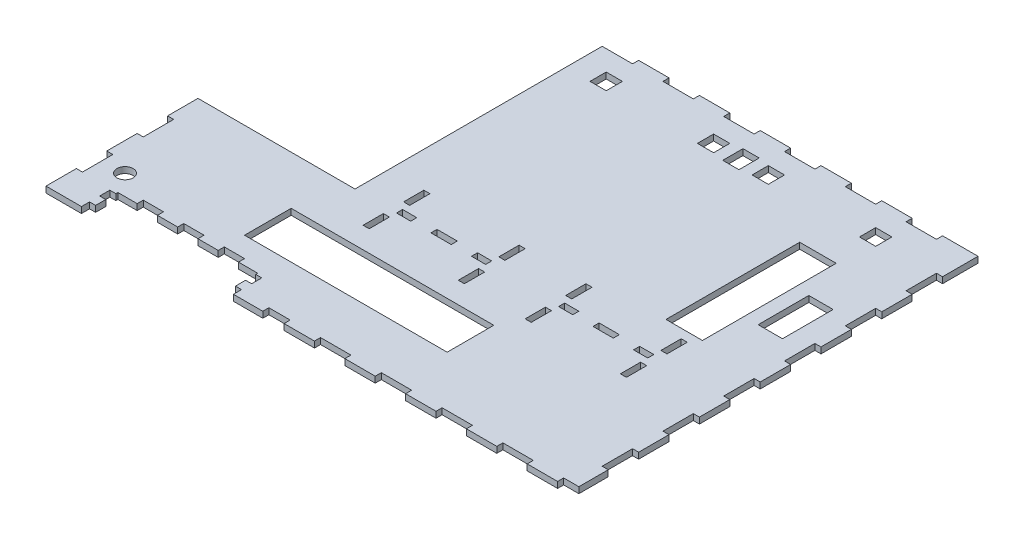
SolidWorks part; units mm, degrees
ref_plane "Alzado" through (0, 0, 0) normal (0, 0, 1) x (1, 0, 0)
ref_plane "Planta" through (0, 0, 0) normal (0, 1, 0) x (1, 0, 0)
ref_plane "Vista lateral" through (0, 0, 0) normal (1, 0, 0) x (0, 0, -1)
sketch "Croquis1" plane through (0, 0, 0) normal (0, 1, 0) x (1, 0, 0)
  line L0 (17.5, 79) -> (20.5, 79)
  line L1 (60, 83) -> (50, 83)
  line L2 (0, 265) -> (17.5, 265) construction
  line L3 (260, 265) -> (260, 247.5)
  line L4 (252.5, 65) -> (237.5, 65)
  line L5 (50, 83) -> (50, 80)
  line L6 (50, 80) -> (40, 80)
  line L7 (40, 80) -> (40, 83)
  line L8 (84.3736, 80) -> (89.5, 80)
  line L9 (40, 83) -> (30, 83)
  line L10 (17.5, 69) -> (20.5, 69)
  line L11 (0, 65) -> (17.5, 65)
  line L12 (92.5, 69) -> (92.5, 65)
  line L13 (20.5, 74) -> (17.5, 74)
  line L14 (92.5, 69) -> (89.5, 69)
  line L15 (30, 83) -> (30, 80)
  line L16 (89.5, 69) -> (89.5, 74)
  line L17 (92.5, 74) -> (92.5, 79)
  line L18 (115, 143) -> (125, 143)
  line L19 (80, 80) -> (84.3736, 80)
  line L20 (89.5, 80) -> (89.5, 79)
  line L21 (30, 80) -> (25.6264, 80)
  line L22 (115, 140) -> (125, 140)
  line L23 (17.5, 69) -> (17.5, 65)
  line L24 (80, 83) -> (80, 80)
  line L25 (89.5, 74) -> (92.5, 74)
  line L26 (70, 83) -> (80, 83)
  line L27 (120, 93) -> (70, 93)
  line L28 (177.5, 65) -> (177.5, 68)
  line L29 (177.5, 68) -> (162.5, 68)
  line L30 (162.5, 68) -> (162.5, 65)
  line L31 (162.5, 65) -> (147.5, 65)
  line L32 (147.5, 65) -> (147.5, 68)
  line L33 (147.5, 68) -> (132.5, 68)
  line L34 (132.5, 68) -> (132.5, 65)
  line L35 (132.5, 65) -> (117.5, 65)
  line L36 (117.5, 65) -> (117.5, 68)
  line L37 (117.5, 68) -> (107, 68)
  line L38 (107, 68) -> (107, 65)
  line L39 (70, 80) -> (70, 83)
  line L40 (92.5, 65) -> (107, 65)
  line L41 (260, 157.5) -> (257, 157.5)
  line L42 (252.5, 68) -> (260, 68)
  line L43 (252.5, 65) -> (252.5, 68)
  line L44 (237.5, 68) -> (237.5, 65)
  line L45 (222.5, 68) -> (237.5, 68)
  line L46 (222.5, 65) -> (222.5, 68)
  line L47 (207.5, 68) -> (207.5, 65)
  line L48 (192.5, 68) -> (207.5, 68)
  line L49 (192.5, 65) -> (192.5, 68)
  line L50 (257, 157.5) -> (257, 142.5)
  line L51 (257, 142.5) -> (260, 142.5)
  line L52 (260, 142.5) -> (260, 127.5)
  line L53 (260, 127.5) -> (257, 127.5)
  line L54 (257, 127.5) -> (257, 112.5)
  line L55 (257, 112.5) -> (260, 112.5)
  line L56 (260, 112.5) -> (260, 97.5)
  line L57 (260, 97.5) -> (257, 97.5)
  line L58 (257, 97.5) -> (257, 82.5)
  line L59 (257, 82.5) -> (260, 82.5)
  line L60 (89.5, 79) -> (92.5, 79)
  line L61 (257, 247.5) -> (260, 247.5)
  line L62 (257, 232.5) -> (257, 247.5)
  line L63 (260, 232.5) -> (257, 232.5)
  line L64 (257, 217.5) -> (260, 217.5)
  line L65 (257, 202.5) -> (257, 217.5)
  line L66 (260, 202.5) -> (257, 202.5)
  line L67 (257, 187.5) -> (260, 187.5)
  line L68 (257, 172.5) -> (257, 187.5)
  line L69 (260, 172.5) -> (257, 172.5)
  line L70 (137.5, 265) -> (137.5, 262)
  line L71 (137.5, 262) -> (152.5, 262)
  line L72 (152.5, 262) -> (152.5, 265)
  line L73 (152.5, 265) -> (167.5, 265)
  line L74 (167.5, 265) -> (167.5, 262)
  line L75 (167.5, 262) -> (182.5, 262)
  line L76 (182.5, 262) -> (182.5, 265)
  line L77 (182.5, 265) -> (197.5, 265)
  line L78 (197.5, 265) -> (197.5, 262)
  line L79 (197.5, 262) -> (212.5, 262)
  line L80 (212.5, 262) -> (212.5, 265)
  line L81 (212.5, 265) -> (227.5, 265)
  line L82 (227.5, 265) -> (227.5, 262)
  line L83 (227.5, 262) -> (242.5, 262)
  line L84 (242.5, 262) -> (242.5, 265)
  line L85 (17.5, 74) -> (17.5, 79)
  line L86 (17.5, 262) -> (17.5, 265) construction
  line L87 (32.5, 262) -> (17.5, 262) construction
  line L88 (32.5, 265) -> (32.5, 262) construction
  line L89 (47.5, 262) -> (47.5, 265) construction
  line L90 (62.5, 262) -> (47.5, 262) construction
  line L91 (62.5, 265) -> (62.5, 262) construction
  line L92 (77.5, 262) -> (77.5, 265) construction
  line L93 (92.5, 262) -> (77.5, 262)
  line L94 (92.5, 265) -> (92.5, 262)
  line L95 (107.5, 262) -> (107.5, 265)
  line L96 (122.5, 262) -> (107.5, 262)
  line L97 (122.5, 265) -> (122.5, 262)
  line L98 (0, 140) -> (3, 140)
  line L99 (3, 140) -> (3, 155) construction
  line L100 (3, 155) -> (0, 155) construction
  line L101 (0, 155) -> (0, 162.5) construction
  line L102 (0, 170) -> (3, 170) construction
  line L103 (3, 170) -> (3, 185) construction
  line L104 (3, 185) -> (0, 185) construction
  line L105 (0, 185) -> (0, 200) construction
  line L106 (0, 200) -> (3, 200) construction
  line L107 (3, 200) -> (3, 215) construction
  line L108 (3, 215) -> (0, 215) construction
  line L109 (0, 215) -> (0, 230) construction
  line L110 (0, 230) -> (3, 230) construction
  line L111 (3, 230) -> (3, 245) construction
  line L112 (3, 245) -> (0, 245) construction
  line L113 (20.5, 69) -> (20.5, 74)
  line L114 (60, 80) -> (70, 80)
  line L115 (60, 83) -> (60, 80)
  line L116 (20.5, 79) -> (20.5, 80)
  line L117 (20.5, 80) -> (25.6264, 80)
  line L118 (70, 93) -> (70, 116)
  line L119 (32.5, 265) -> (47.5, 265) construction
  line L120 (3, 80) -> (0, 80)
  line L121 (3, 95) -> (3, 80)
  line L122 (0, 95) -> (3, 95)
  line L123 (3, 110) -> (0, 110)
  line L124 (3, 125) -> (3, 110)
  line L125 (0, 125) -> (3, 125)
  line L126 (70, 116) -> (170, 116)
  line L127 (170, 116) -> (170, 93)
  line L128 (62.5, 265) -> (77.5, 265) construction
  line L129 (92.5, 265) -> (107.5, 265)
  line L130 (122.5, 265) -> (137.5, 265)
  line L131 (170, 93) -> (120, 93)
  line L132 (195, 143) -> (205, 143)
  line L133 (98, 156.5) -> (98, 146.5)
  line L134 (242.5, 265) -> (260, 265)
  line L135 (0, 245) -> (0, 265) construction
  line L136 (98, 136.5) -> (95, 136.5)
  line L137 (95, 136.5) -> (95, 126.5)
  line L138 (95, 126.5) -> (98, 126.5)
  line L139 (0, 125) -> (0, 140)
  line L140 (0, 95) -> (0, 110)
  line L141 (0, 65) -> (0, 80)
  line L142 (3, 140) -> (77.5, 140)
  line L143 (105, 140) -> (98, 140)
  line L144 (98, 140) -> (98, 143)
  line L145 (98, 143) -> (105, 143)
  line L146 (105, 143) -> (105, 140)
  line L147 (95, 156.5) -> (98, 156.5)
  line L148 (95, 146.5) -> (95, 156.5)
  line L149 (98, 146.5) -> (95, 146.5)
  line L150 (192.5, 65) -> (177.5, 65)
  line L151 (222.5, 65) -> (207.5, 65)
  line L152 (260, 82.5) -> (260, 68)
  line L153 (142, 146.5) -> (145, 146.5)
  line L154 (145, 146.5) -> (145, 156.5)
  line L155 (260, 172.5) -> (260, 157.5)
  line L156 (260, 202.5) -> (260, 187.5)
  line L157 (260, 232.5) -> (260, 217.5)
  line L158 (145, 156.5) -> (142, 156.5)
  line L159 (98, 126.5) -> (98, 136.5)
  line L160 (77.5, 140) -> (77.5, 155)
  line L161 (142, 156.5) -> (142, 146.5)
  line L162 (142, 126.5) -> (142, 136.5)
  line L163 (145, 126.5) -> (142, 126.5)
  line L164 (145, 136.5) -> (145, 126.5)
  line L165 (142, 136.5) -> (145, 136.5)
  line L166 (178, 156.5) -> (178, 146.5)
  line L167 (175, 156.5) -> (178, 156.5)
  line L168 (135, 143) -> (135, 140)
  line L169 (142, 143) -> (135, 143)
  line L170 (142, 140) -> (142, 143)
  line L171 (135, 140) -> (142, 140)
  line L172 (125, 143) -> (125, 140)
  line L173 (115, 140) -> (115, 143)
  line L174 (185, 140) -> (178, 140)
  line L175 (175, 146.5) -> (175, 156.5)
  line L176 (178, 140) -> (178, 143)
  line L177 (178, 146.5) -> (175, 146.5)
  line L178 (222, 146.5) -> (225, 146.5)
  line L179 (225, 146.5) -> (225, 156.5)
  line L180 (222, 140) -> (222, 143)
  line L181 (225, 156.5) -> (222, 156.5)
  line L182 (222, 156.5) -> (222, 146.5)
  line L183 (178, 136.5) -> (175, 136.5)
  line L184 (175, 136.5) -> (175, 126.5)
  line L185 (178, 143) -> (185, 143)
  line L186 (175, 126.5) -> (178, 126.5)
  line L187 (205, 140) -> (205, 143)
  line L188 (185, 143) -> (185, 140)
  line L189 (178, 126.5) -> (178, 136.5)
  line L190 (222, 126.5) -> (222, 136.5)
  line L191 (225, 126.5) -> (222, 126.5)
  line L192 (225, 136.5) -> (225, 126.5)
  line L193 (222, 136.5) -> (225, 136.5)
  line L194 (0, 170) -> (0, 162.5) construction
  line L195 (215, 143) -> (215, 140)
  line L196 (77.5, 155) -> (77.5, 262)
  line L197 (93.5, 248) -> (93.5, 244) construction
  line L198 (89.5, 252) -> (97.5, 252)
  line L199 (215, 140) -> (222, 140)
  line L200 (195, 140) -> (205, 140)
  line L201 (89.5, 252) -> (89.5, 244)
  line L202 (89.5, 244) -> (97.5, 244)
  line L203 (97.5, 252) -> (97.5, 244)
  line L204 (222, 143) -> (215, 143)
  line L205 (195, 140) -> (195, 143)
  line L206 (89.5, 252) -> (97.5, 244) construction
  line L207 (89.5, 244) -> (97.5, 252) construction
  line L208 (146.5, 248) -> (146.5, 244) construction
  line L209 (142.5, 252) -> (150.5, 252)
  line L210 (142.5, 252) -> (142.5, 244)
  line L211 (142.5, 244) -> (150.5, 244)
  line L212 (150.5, 252) -> (150.5, 244)
  line L213 (142.5, 252) -> (150.5, 244) construction
  line L214 (142.5, 244) -> (150.5, 252) construction
  line L215 (173.5, 248) -> (173.5, 244) construction
  line L216 (169.5, 252) -> (177.5, 252)
  line L217 (169.5, 252) -> (169.5, 244)
  line L218 (169.5, 244) -> (177.5, 244)
  line L219 (177.5, 252) -> (177.5, 244)
  line L220 (169.5, 252) -> (177.5, 244) construction
  line L221 (169.5, 244) -> (177.5, 252) construction
  line L222 (226.5, 248) -> (226.5, 244) construction
  line L223 (222.5, 252) -> (230.5, 252)
  line L224 (222.5, 252) -> (222.5, 244)
  line L225 (222.5, 244) -> (230.5, 244)
  line L226 (230.5, 252) -> (230.5, 244)
  line L227 (222.5, 252) -> (230.5, 244) construction
  line L228 (222.5, 244) -> (230.5, 252) construction
  dimension "D6" = 10
  dimension "D14" = 8
  dimension "D16" = 3
  dimension "D70" = 8
  dimension "D7" = 50
  dimension "D8" = 10
  dimension "D9" = 10
  dimension "D10" = 23
  dimension "D11" = 100
  dimension "D12" = 16
  dimension "D13" = 10
  dimension "D15" = 14
  dimension "D17" = 15
  dimension "D18" = 3
  dimension "D19" = 15
  dimension "D20" = 15
  dimension "D21" = 14.5
  dimension "D22" = 15
  dimension "D23" = 74.5
  dimension "D24" = 15
  dimension "D25" = 3
  dimension "D26" = 15
  dimension "D27" = 15
  dimension "D28" = 15
  dimension "D29" = 15
  dimension "D30" = 15
  dimension "D31" = 15
  dimension "D32" = 15
  dimension "D33" = 15
  dimension "D34" = 3
  dimension "D35" = 15
  dimension "D36" = 15
  dimension "D37" = 15
  dimension "D38" = 15
  dimension "D39" = 15
  dimension "D40" = 15
  dimension "D41" = 15
  dimension "D42" = 15
  dimension "D43" = 3
  dimension "D44" = 3
  dimension "D45" = 17.5
  dimension "D46" = 17.5
  dimension "D47" = 15
  dimension "D48" = 3
  dimension "D49" = 15
  dimension "D50" = 15
  dimension "D51" = 15
  dimension "D52" = 3
  dimension "D53" = 15
  dimension "D54" = 15
  dimension "D55" = 15
  dimension "D56" = 15
  dimension "D57" = 15
  dimension "D58" = 3
  dimension "D59" = 17.5
  dimension "D60" = 4
  dimension "D61" = 10
  dimension "D62" = 65
  dimension "D63" = 8
  dimension "D64" = 8
  dimension "D65" = 15
  dimension "D66" = 107
  dimension "D67" = 3
  dimension "D68" = 14
  dimension "D69" = 69
  dimension "D71" = 3
  dimension "D72" = 8
  dimension "D73" = 8
  dimension "D74" = 27
  dimension "D75" = 53
  dimension "D76" = 8
  dimension "D77" = 8
extrude "Saliente-Extruir1" add sketch "Croquis1" along normal blind 3
sketch "Sketch1" plane through (0, 0, 0) normal (0, -1, 0) x (1, 0, 0)
  line L0 (247, -181.5) -> (247, -206.5)
  line L1 (247, -206.5) -> (235, -206.5)
  line L2 (235, -206.5) -> (235, -181.5)
  line L3 (235, -181.5) -> (247, -181.5)
  line L4 (260, -187.5) -> (260, -202.5) construction
  line L6 (210, -161) -> (228, -161)
  line L7 (210, -161) -> (210, -227)
  line L8 (210, -227) -> (228, -227)
  line L9 (228, -161) -> (228, -227)
  line L10 (210, -161) -> (228, -227) construction
  line L11 (210, -227) -> (228, -161) construction
  line L12 (227.5, -265) -> (212.5, -265) construction
  line L13 (219, -194) -> (228, -194) construction
  line L14 (235, -194) -> (247, -194) construction
  point P4 (260, -195)
  point P7 (219, -194)
  dimension "D1" = 13
  dimension "D2" = 25
  dimension "D3" = 12
  dimension "D4" = 7
  dimension "D5" = 18
  dimension "D6" = 66
  dimension "D7" = 38
extrude "Cut-Extrude2" cut sketch "Sketch1" against normal blind 10
sketch "Sketch2" plane through (0, 3, 0) normal (0, 1, 0) x (1, 0, 0)
  line L0 (169.5, 248) -> (150.5, 248) construction
  line L1 (169.5, 252) -> (169.5, 244) construction
  line L2 (150.5, 244) -> (150.5, 252) construction
  line L4 (164, 243) -> (156, 243)
  line L5 (164, 243) -> (164, 253)
  line L6 (164, 253) -> (156, 253)
  line L7 (156, 243) -> (156, 253)
  line L8 (164, 243) -> (156, 253) construction
  line L9 (164, 253) -> (156, 243) construction
  point P6 (160, 248)
  dimension "D1" = 8
  dimension "D2" = 10
extrude "Cut-Extrude3" cut sketch "Sketch2" against normal blind 10
sketch "Sketch3" plane through (0, 3, 0) normal (0, 1, 0) x (1, 0, 0)
  line L0 (20.5, 80) -> (30, 80) construction
  circle A0 centre (14, 90) radius 4
  point P2 (25.25, 80)
  dimension "D1" = 8
  dimension "D2" = 14
  dimension "D3" = 10
extrude "Cut-Extrude4" cut sketch "Sketch3" against normal blind 10
